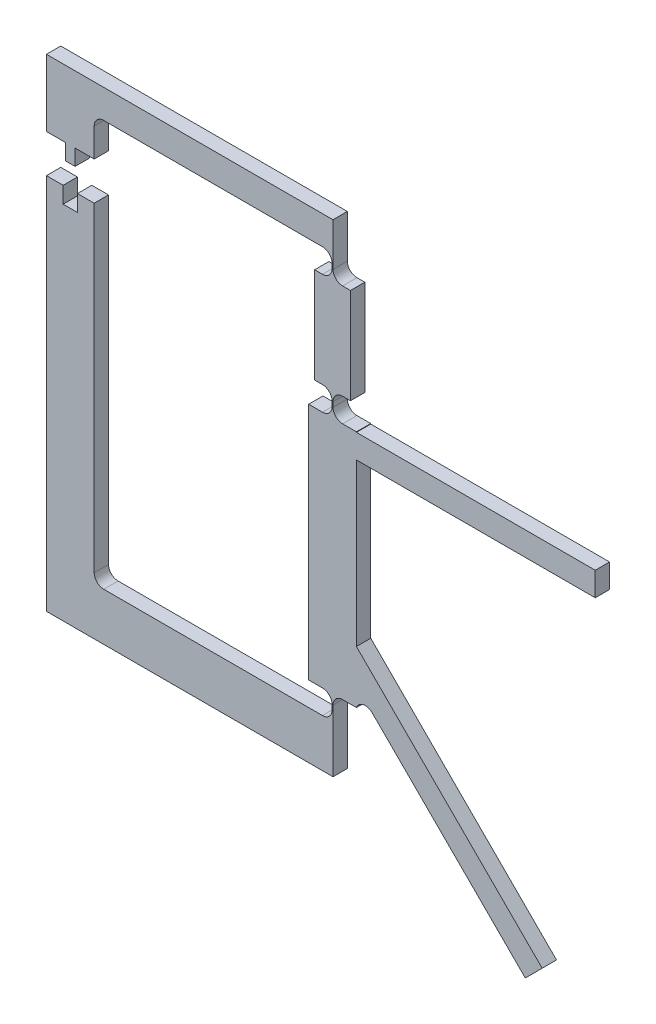
SolidWorks part; units mm, degrees
ref_plane "Front Plane" through (0, 0, 0) normal (0, 0, 1) x (1, 0, 0)
ref_plane "Top Plane" through (0, 0, 0) normal (0, 1, 0) x (1, 0, 0)
ref_plane "Right Plane" through (0, 0, 0) normal (1, 0, 0) x (0, 0, -1)
sketch "Sketch2" plane through (0, 0, 0) normal (0, 0, 1) x (1, 0, 0)
  line L0 (0, 0) -> (0, 79)
  line L1 (0, 0) -> (60, 0)
  line L4 (10, 10) -> (10, 79)
  line L5 (10, 79) -> (6.5, 79)
  line L6 (59.8, 10) -> (59.8, 15)
  line L7 (59.8, 15) -> (54.9, 15)
  line L8 (54.9, 15) -> (54.9, 65)
  line L9 (54.9, 65) -> (59.8, 65)
  line L10 (59.8, 65) -> (59.8, 70)
  line L11 (59.8, 70) -> (56.15, 70)
  line L12 (56.15, 70) -> (56.15, 90)
  line L13 (56.15, 90) -> (59.8, 90)
  line L14 (59.8, 90) -> (59.8, 95)
  line L24 (64.9, 65) -> (60, 65)
  line L25 (60, 65) -> (60, 70)
  line L26 (60, 70) -> (63.65, 70)
  line L27 (63.65, 70) -> (63.65, 90)
  line L28 (63.65, 90) -> (60, 90)
  line L29 (60, 90) -> (60, 95)
  line L32 (60, 101) -> (0, 101)
  line L33 (0, 101) -> (0, 91)
  line L35 (10, 10) -> (59.8, 10)
  line L37 (60, 10) -> (60, 15)
  line L38 (60, 15) -> (64.9, 15)
  line L40 (59.8, 10) -> (59.9, 10) construction
  line L41 (59.9, 10) -> (59.9, 15) construction
  line L42 (59.9, 10) -> (60, 10) construction
  line L43 (59.8, 65) -> (59.9, 65) construction
  line L44 (59.9, 65) -> (59.9, 70) construction
  line L45 (59.9, 65) -> (60, 65) construction
  line L46 (60, 95) -> (60, 101)
  line L47 (64.9, 65) -> (64.9, 64.9)
  line L48 (60, 10) -> (60, 0)
  line L49 (10, 95) -> (59.8, 95)
  line L51 (64.9, 26.0711) -> (103.7909, -12.8197)
  line L53 (0, 91) -> (0, 87)
  line L54 (0, 87) -> (4, 87)
  line L55 (10, 95) -> (10, 87)
  line L56 (103.7909, -12.8197) -> (100.2554, -16.3553)
  line L57 (100.2554, -16.3553) -> (64.9, 19)
  line L58 (64.9, 64.9) -> (114.9, 64.9)
  line L59 (114.9, 64.9) -> (114.9, 59.9)
  line L60 (114.9, 59.9) -> (64.9, 59.9)
  line L61 (64.9, 59.9) -> (64.9, 26.0711)
  line L62 (64.9, 19) -> (64.9, 15)
  line L63 (4, 83.6667) -> (4, 87)
  line L64 (4, 83.6667) -> (6, 83.6667)
  line L66 (6, 83.6667) -> (6, 87)
  line L67 (4, 83.6667) -> (6, 87) construction
  line L68 (4, 87) -> (6, 83.6667) construction
  line L70 (3.5, 79) -> (3.5, 75.5667)
  line L71 (6.5, 79) -> (6.5, 75.5667)
  line L72 (3.5, 75.5667) -> (6.5, 75.5667)
  line L73 (3.5, 79) -> (0, 79)
  line L74 (6, 87) -> (10, 87)
  point P44 (6.25, 90.7019)
  point P45 (5, 85.3333)
  point P46 (6.25, 90.5667)
  dimension "D2" = 60
  dimension "D3" = 5
  dimension "D4" = 5
  dimension "D5" = 0.2
  dimension "D6" = 20
  dimension "D7" = 5
  dimension "D8" = 0.2
  dimension "D9" = 50
  dimension "D10" = 5
  dimension "D14" = 0.2
  dimension "D17" = 60
  dimension "D18" = 10
  dimension "D20" = 20
  dimension "D22" = 50
  dimension "D11" = 10
  dimension "D12" = 7.5
  dimension "D13" = 10
  dimension "D15" = 69
  dimension "D16" = 6
  dimension "D19" = 14
  dimension "D21" = 50
  dimension "D23" = 50
  dimension "D24" = 45
  dimension "D25" = 5
  dimension "D26" = 5
  dimension "D27" = 0.1
  dimension "D28" = 4
  dimension "D29" = 3.3333
  dimension "D30" = 2
  dimension "D31" = 3
  dimension "D32" = 3.4333
  dimension "D33" = 3.5
  dimension "D34" = 4
extrude "Boss-Extrude1" add sketch "Sketch2" along normal blind 3
fillet "Fillet1" radius 2 13 edges at (59.8, 15, 1.5) (60, 15, 1.5) (60, 70, 1.5) (60, 65, 1.5) (59.8, 65, 1.5) (59.8, 70, 1.5) (59.8, 95, 1.5) (60, 90, 1.5) (59.8, 90, 1.5) (10, 10, 1.5) (10, 95, 1.5) (59.8, 10, 1.5) (64.9, 19, 1.5)
equation "\"C.h\"= 0.006m"
equation "\"C.L\"= 0.05m"
equation "\"D2@Sketch2\"=\"C.L\"+\"S.h\""
equation "\"c_L\"= 0.005m"
equation "\"D3@Sketch2\"=\"c_L\""
equation "\"D4@Sketch2\"=\"c_L\""
equation "\"c_h\"= 0.0002m"
equation "\"D5@Sketch2\"=\"c_h\""
equation "\"B.L\"= 0.02m"
equation "\"D6@Sketch2\"=\"B.L\""
equation "\"b_L\"= 0.005m"
equation "\"b_h\"= 0.0002m"
equation "\"D7@Sketch2\"=\"b_L\""
equation "\"D8@Sketch2\"=\"b_h\""
equation "\"A.L\"= 0.05m"
equation "\"D9@Sketch2\"=\"A.L\""
equation "\"A.h\"= 0.01m"
equation "\"a_h\"= 0.0002m"
equation "\"a_L\"= 0.005m"
equation "\"D10@Sketch2\"=\"a_L\""
equation "\"D14@Sketch2\"=\"a_h\""
equation "\"S.h\"= 0.01m"
equation "\"S.L\"= 0.08m"
equation "\"D17@Sketch2\"=\"C.L\"+\"S.h\""
equation "\"S.t\"=0.3"
equation "\"D18@Sketch2\"=\"S.h\""
equation "\"D20@Sketch2\"=\"B.L\""
equation "\"D22@Sketch2\"=\"A.L\""
equation "\"A.w\"= 0.05m"
equation "\"A.v\"= 0.05m"
equation "\"A.theta_max\"= 0.2618mm"
equation "\"B.h\"= 0.0075m"
equation "\"C.d\"= 0.003m"
equation "\"C.wmax\"= 0.008m"
equation "\"a_d\"= 0.003m"
equation "\"b_d\"= 0.003m"
equation "\"c_d\"= 0.003m"
equation "\"D11@Sketch2\"=\"A.h\""
equation "\"D12@Sketch2\"=\"B.h\""
equation "\"D13@Sketch2\"=\"S.h\""
equation "\"D15@Sketch2\"=\"A.L\"+\"B.L\"+\"a_L\"+\"b_L\"+\"c_L\"-\"C.wmax\"*2"
equation "\"A.d\"= 0.003m"
equation "\"D1@Boss-Extrude1\"=\"A.d\""
equation "\"D16@Sketch2\"=\"C.h\""
equation "\"D19@Sketch2\"=\"C.h\"+\"C.wmax\""
equation "\"D21@Sketch2\"=\"A.v\""
equation "\"D23@Sketch2\"=\"A.w\""
equation "\"A.delta\"= 45.0001"
equation "\"D24@Sketch2\"=\"A.delta\""
equation "\"D25@Sketch2\"=\"A.h\"/2"
equation "\"D26@Sketch2\"=\"A.h\"/2"
equation "\"D29@Sketch2\"=\"S.h\"/3"
equation "\"D30@Sketch2\"=\"S.h\"/5"
equation "\"D31@Sketch2\"=\"S.h\"/5+1"
equation "\"D32@Sketch2\"=\"S.h\"/3+0.1"
equation "\"D33@Sketch2\"=\"S.h\"/2-(\"S.h\"/5+1)/2"
equation "\"D34@Sketch2\"=\"S.h\"/2-(\"S.h\"/5)/2"
